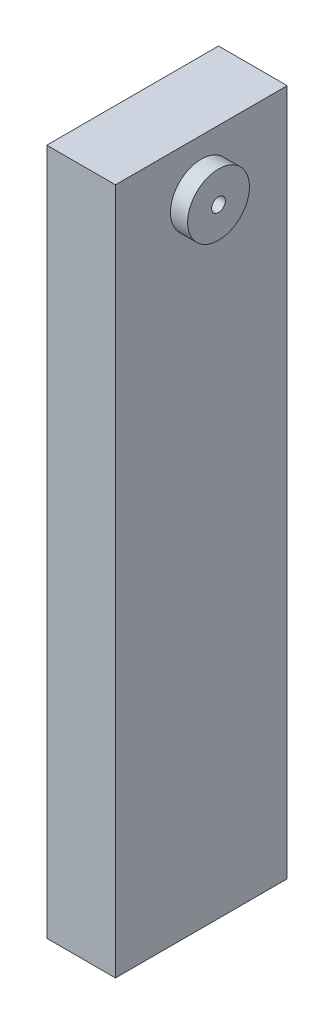
SolidWorks part; units mm, degrees
ref_plane "Front Plane" through (0, 0, 0) normal (0, 0, 1) x (1, 0, 0)
ref_plane "Top Plane" through (0, 0, 0) normal (0, 1, 0) x (1, 0, 0)
ref_plane "Right Plane" through (0, 0, 0) normal (1, 0, 0) x (0, 0, -1)
sketch "Sketch1" plane through (0, 0, 0) normal (0, 1, 0) x (1, 0, 0)
  line L1 (50, -125) -> (-50, -125)
  line L2 (50, -125) -> (50, 125)
  line L3 (50, 125) -> (-50, 125)
  line L4 (-50, -125) -> (-50, 125)
  line L5 (50, -125) -> (-50, 125) construction
  line L6 (50, 125) -> (-50, -125) construction
  point P0 (0, 0)
  dimension "D1" = 250
  dimension "D2" = 100
extrude "Boss-Extrude1" add sketch "Sketch1" along normal blind 1000
sketch "Sketch2" plane through (50, 0, 0) normal (1, 0, 0) x (0, 0, -1)
  line L0 (0, 0) -> (0, 50000) construction
  line L1 (-125, 1000) -> (125, 1000) construction
  circle A0 centre (0, 925) radius 45
  dimension "D1" = 90
  dimension "D2" = 75
extrude "Boss-Extrude2" add sketch "Sketch2" along normal blind 25
sketch "Sketch3" plane through (75, 0, 0) normal (1, 0, 0) x (0, 0, -1)
  circle A0 centre (0, 925) radius 10
  dimension "D1" = 20
extrude "Cut-Extrude1" cut sketch "Sketch3" against normal blind 25
